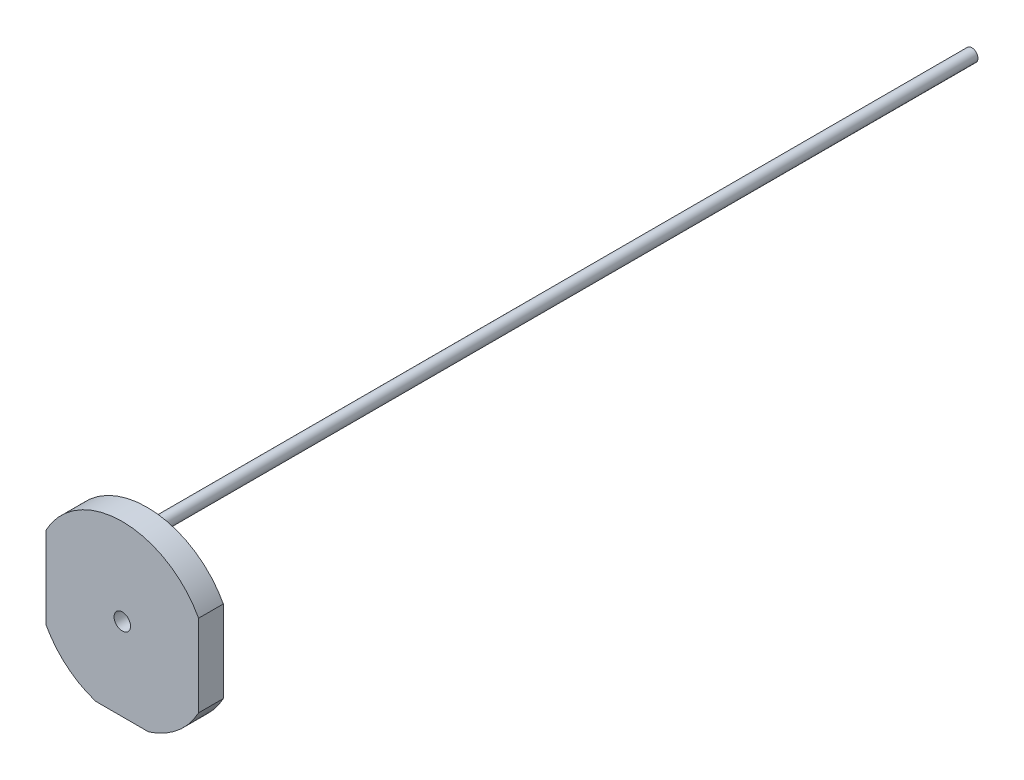
SolidWorks part; units mm, degrees
ref_plane "前视基准面" through (0, 0, 0) normal (0, 0, 1) x (1, 0, 0)
ref_plane "上视基准面" through (0, 0, 0) normal (0, 1, 0) x (1, 0, 0)
ref_plane "右视基准面" through (0, 0, 0) normal (1, 0, 0) x (0, 0, -1)
other "Configuration Table"
sketch "草图1" plane through (0, 0, 0) normal (0, 0, 1) x (1, 0, 0)
  line L0 (-18.5, 9.9373) -> (-18.5, -9.9373)
  line L1 (18.5, 9.9373) -> (18.5, -9.9373)
  line L2 (0, 0) -> (0, -20) construction
  line L5 (-6.4031, -20) -> (6.4031, -20)
  arc A0 (-18.5, -9.9373) -> (-6.4031, -20) centre (0, 0) ccw
  arc A1 (6.4031, -20) -> (18.5, -9.9373) centre (0, 0) ccw
  arc A2 (18.5, 9.9373) -> (-18.5, 9.9373) centre (0, 0) ccw
  circle A3 centre (0, 0) radius 2
  circle A4 centre (0, 16) radius 1.5
  dimension "D2" = 21
  dimension "D4" = 3
  dimension "D5" = 4
  dimension "D1" = 20
  dimension "D3" = 37
  dimension "D6" = 16
extrude "凸台-拉伸1" add sketch "草图1" against normal blind 6
extrude "凸台-拉伸2" add sketch "草图1<4>" against normal blind 206 contours A4
sketch "草图1<4>" plane through (0, 0, 0) normal (0, 0, 1) x (1, 0, 0) same geometry as "草图1"
